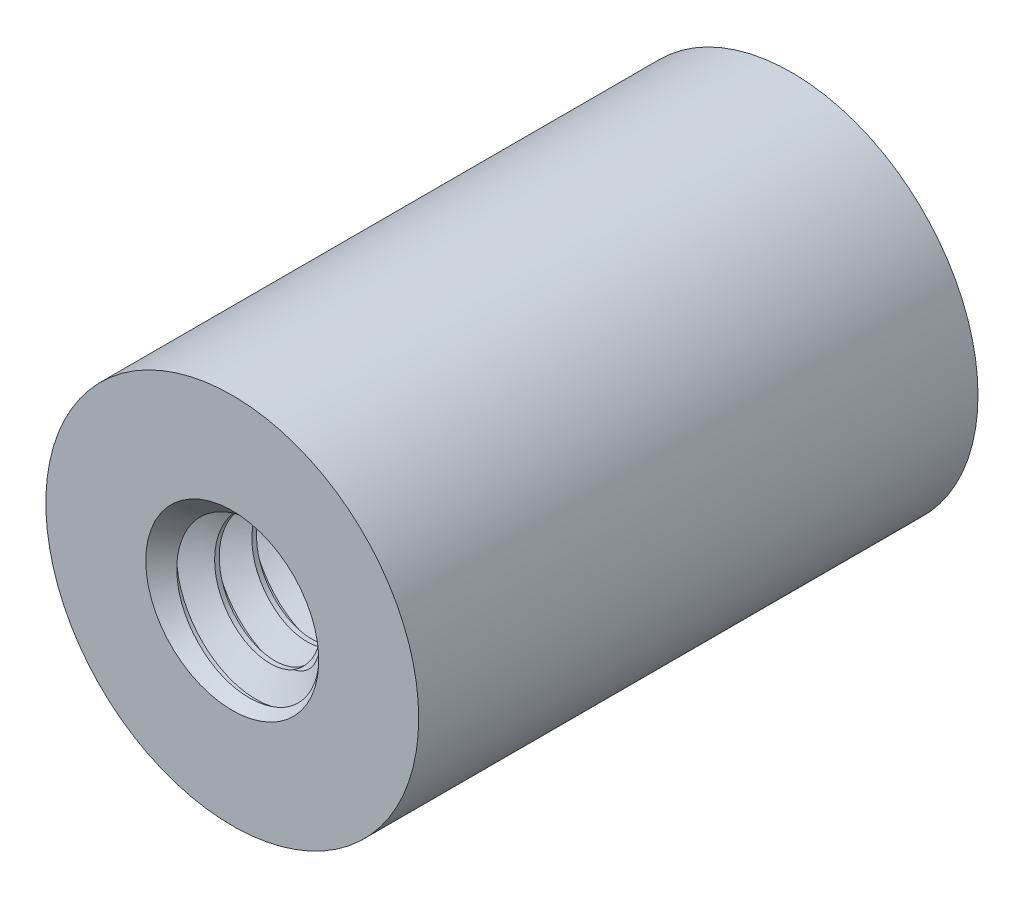
SolidWorks part; units mm, degrees
ref_plane "Front Plane" through (0, 0, 0) normal (0, 0, 1) x (1, 0, 0)
ref_plane "Top Plane" through (0, 0, 0) normal (0, 1, 0) x (1, 0, 0)
ref_plane "Right Plane" through (0, 0, 0) normal (1, 0, 0) x (0, 0, -1)
sketch "Sketch3" plane through (0, 0, 0) normal (1, 0, 0) x (0, 0, -1)
  line L0 (-4.7625, 0) -> (4.7625, 0) construction
  line L1 (0, 3.175) -> (0, -3.175) construction
  line L2 (-4.7625, 1.4224) -> (-4.7625, -1.4224) construction
  point P2 (-7.9375, 0)
  point P3 (7.9375, 0)
  dimension "D1" = 12.7
  dimension "Length" = 9.525
  dimension "Min Thread Length" = 12.7
  dimension "Thread Dia" = 2.8448
  dimension "OD" = 6.35
sketch "Sketch1" plane through (0, 0, 0) normal (0, 0, 1) x (1, 0, 0)
  circle A1 centre (0, 0) radius 1.4224
  circle A2 centre (0, 0) radius 3.175
extrude "Extrude1" add sketch "Sketch1" along normal up to vertex (4.7625 mm away) and the other way up to vertex (4.7625 mm away) up to point (0, 0, 4.7625) other way up to point (0, 0, -4.7625)
sketch "Sketch11" plane through (0, 0, -4.7625) normal (0, 0, -1) x (-1, 0, 0)
  circle A0 centre (0, 0) radius 1.4224 construction
  circle A1 centre (0, 0) radius 1.4224
curve "Helix/Spiral1" pitch 0.635 height 10.16 radius 1.4224 centre (0, 0, -4.7625) axis (0, 0, 1) start towards (0, 1, 0) parameters "Pitch"=0.635
sketch "Sketch12" plane through (0, 0, 0) normal (1, 0, 0) x (0, 0, -1)
  line L0 (5.3181, 1.4224) -> (4.7625, 1.4224)
  line L1 (5.3181, 1.4224) -> (5.08, 1.01)
  line L2 (5.08, 1.01) -> (5.0006, 1.01)
  line L3 (5.0006, 1.01) -> (4.7625, 1.4224)
  line L4 (5.0403, 1.01) -> (5.0403, 1.4224) construction
  line L5 (5.1991, 1.2162) -> (4.8816, 1.2162) construction
  dimension "D1" = 0.0794
  dimension "D2" = 0.3175
  dimension "D3" = 60
sweep "Sweep1" add profiles "Sketch12" path "Helix/Spiral1"
sketch "Sketch6" plane through (0, 0, -4.7625) normal (0, 0, -1) x (-1, 0, 0)
  circle A1 centre (0, 0) radius 3.175
  circle A2 centre (0, 0) radius 3.175
  dimension "D1" = 0
extrude "Extrude2" cut sketch "Sketch6" along normal through all
sketch "Sketch7" plane through (0, 0, -4.7625) normal (0, 0, -1) x (-1, 0, 0)
  circle A2 centre (0, 0) radius 1.4732
  circle A3 centre (0, 0) radius 1.4732
  dimension "D1" = 0.0508
extrude "Extrude3" cut sketch "Sketch7" against normal through all draft 43
mirror "Mirror1" about plane through (0, 0, 0) normal (0, 0, 1) of "Extrude2", "Extrude3"
sketch "Sketch9" [suppressed] plane through (0, 0, 0) normal (1, 0, 0) x (0, 0, -1)
  line L1 (-6.35, 1.4732) -> (6.35, 1.4732)
  line L2 (-6.35, 1.4732) -> (-6.35, 0)
  line L3 (-6.35, 0) -> (6.35, 0)
  line L4 (6.35, 1.4732) -> (6.35, 0)
  line L7 (-12.7, 0) -> (12.7, 0) construction
revolve "Revolve" [suppressed] add sketch "Sketch9" angle 360 about L0
sketch "Sketch10" [suppressed] plane through (0, 0, 0) normal (1, 0, 0) x (0, 0, -1)
  line L0 (12.7, 1.4224) -> (6.35, 1.4224)
  line L1 (-12.7, 1.4224) -> (-6.35, 1.4224)
  line L2 (6.35, 1.4224) -> (6.35, -1.4224)
  line L3 (-12.7, -1.4732) -> (-6.35, -1.4732)
  line L4 (-6.35, 1.4224) -> (-6.35, -1.4732)
  line L5 (6.35, -1.4224) -> (12.7, -1.4224)
equation "\"D1@Sketch3\" = \"Min Thread Length@Sketch3\""
equation "\"D3@Helix/Spiral1\" = \"Length@Sketch3\"+\"Pitch@Helix/Spiral1\""
equation "\"D1@Sketch12\" = \"Pitch@Helix/Spiral1\"*.125"
equation "\"D2@Sketch12\" = \"Pitch@Helix/Spiral1\"*.5"
